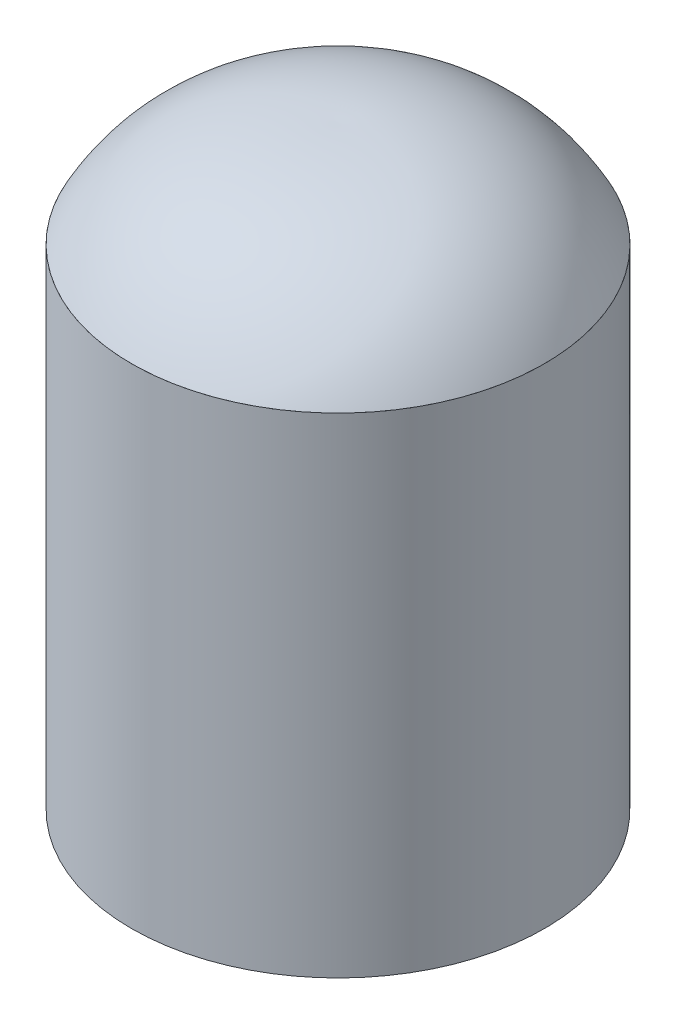
SolidWorks part; units mm, degrees
ref_plane "Front Plane" through (0, 0, 0) normal (0, 0, 1) x (1, 0, 0)
ref_plane "Top Plane" through (0, 0, 0) normal (0, 1, 0) x (1, 0, 0)
ref_plane "Right Plane" through (0, 0, 0) normal (1, 0, 0) x (0, 0, -1)
sketch "Sketch1" plane through (0, 0, 0) normal (0, 0, 1) x (1, 0, 0)
  line L0 (0, 0) -> (0, -87.884)
  line L1 (0, 0) -> (-37.084, 0)
  line L2 (0, 0) -> (0, 19.05)
  line L3 (0, -87.884) -> (-37.084, -87.884)
  line L4 (0, -87.884) -> (0, -124.968)
  line L5 (-37.084, 0) -> (-37.084, -87.884)
  line L6 (-31.75, 0) -> (-31.75, -87.884)
  arc A1 (-37.084, -87.884) -> (0, -124.968) centre (0, -87.884) ccw
  spline S0 degree 2 poles (0, 19.05) (-26.261, 19.8039) (-37.084, 0) knots 0 0 0 1 1 1
  point P11 (-25.4, 17.2882)
  point P12 (-26.5727, 11.4793)
  point P13 (-31.3937, 7.9117)
  dimension "D1" = 87.884
  dimension "D2" = 37.084
  dimension "D3" = 19.05
  dimension "D4" = 37.084
  dimension "D5" = 37.084
  dimension "D6" = 31.75
revolve "Revolve1" add sketch "Sketch1" angle 360 about L2 region at (-14.9309, 8.0901, 0)
revolve "Revolve2" add sketch "Sketch1<3>" angle 360 about L0 region at (-34.417, -43.942, 0)
sketch "Sketch1<3>" plane through (0, 0, 0) normal (0, 0, 1) x (1, 0, 0) same geometry as "Sketch1"
